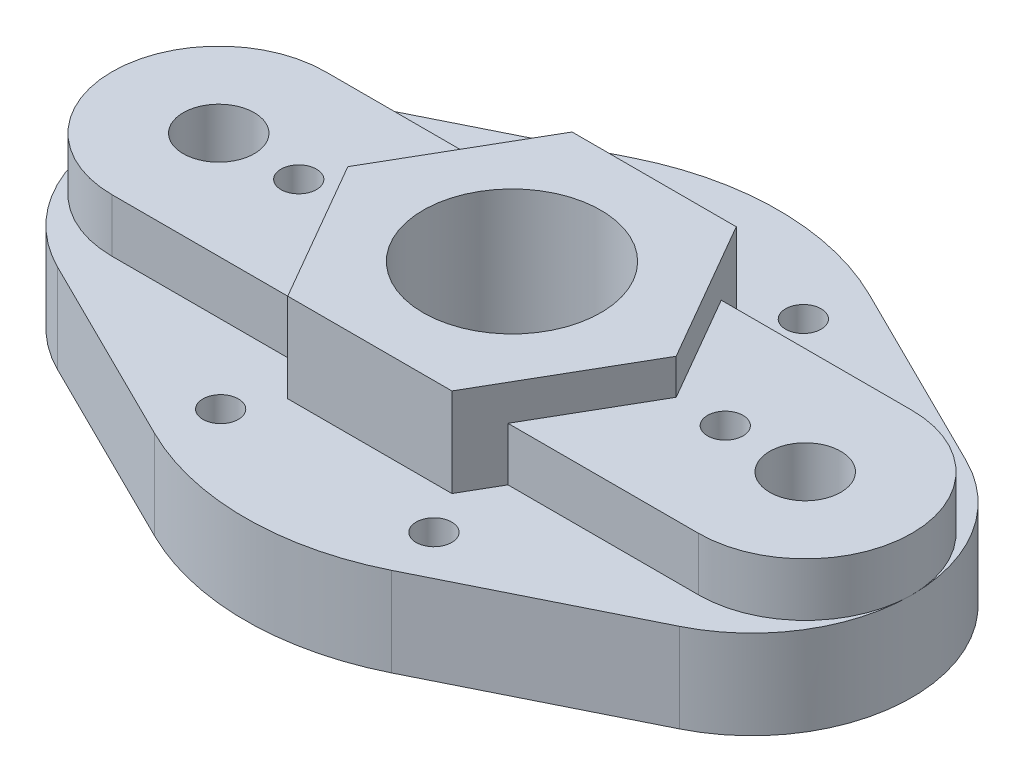
SolidWorks part; units mm, degrees
ref_plane "前视基准面" through (0, 0, 0) normal (0, 0, 1) x (1, 0, 0)
ref_plane "上视基准面" through (0, 0, 0) normal (0, 1, 0) x (1, 0, 0)
ref_plane "右视基准面" through (0, 0, 0) normal (1, 0, 0) x (0, 0, -1)
other "Configuration Table"
sketch "草图2" plane through (0, 0, 0) normal (0, 1, 0) x (1, 0, 0)
  line L0 (0, 0) -> (0, 24.5098) construction
  line L1 (0, 0) -> (45, 0) construction
  line L2 (35, 16.1245) -> (13.3333, 26.8742)
  line L3 (-35, 16.1245) -> (-13.3333, 26.8742)
  line L4 (-35, -16.1245) -> (-13.3333, -26.8742)
  line L5 (35, -16.1245) -> (13.3333, -26.8742)
  line L6 (-33, 0) -> (33, 0) construction
  line L7 (-33, 12) -> (33, 12)
  line L8 (-33, -12) -> (33, -12)
  line L10 (18.4752, 0) -> (9.2376, 16)
  line L11 (9.2376, 16) -> (-9.2376, 16)
  line L12 (-9.2376, 16) -> (-18.4752, 0)
  line L13 (-18.4752, 0) -> (-9.2376, -16)
  line L14 (-9.2376, -16) -> (9.2376, -16)
  line L15 (9.2376, -16) -> (18.4752, 0)
  arc A0 (35, -16.1245) -> (35, 16.1245) centre (27, 0) ccw
  arc A1 (13.3333, 26.8742) -> (-13.3333, 26.8742) centre (0, 0) ccw
  arc A2 (-35, -16.1245) -> (-35, 16.1245) centre (-27, 0) cw
  arc A3 (13.3333, -26.8742) -> (-13.3333, -26.8742) centre (0, 0) cw
  arc A4 (-33, 12) -> (-33, -12) centre (-33, 0) ccw
  arc A5 (33, -12) -> (33, 12) centre (33, 0) ccw
  circle A6 centre (0, 0) radius 16 construction
  point P16 (0, -30)
  point P17 (0, 30)
  point P18 (45, 0)
  point P19 (-45, 0)
  point P22 (0, 0)
  dimension "D1" = 18
  dimension "D2" = 30
  dimension "D3" = 60
  dimension "D4" = 90
  dimension "D5" = 24
  dimension "D6" = 32
extrude "凸台-拉伸1" add sketch "草图2" along normal blind 10 contours A5 L8 L15 L14 L13 A4 A2 L4 A3 L5 A0 | A5 A0 L2 A1 L3 A2 A4 L7 L12 L11 L10 region at (0, 0, -18.9941) region at (0, 0, 18.9941)
extrude "凸台-拉伸2" add sketch "草图2<3>" along normal blind 16 contours L7 A4 L8 L13 L12 | L8 A5 L7 L10 L15 region at (28.7758, 0, 0) region at (-28.7758, 0, 0)
sketch "草图2<3>" plane through (0, 0, 0) normal (0, 1, 0) x (1, 0, 0) same geometry as "草图2"
extrude "凸台-拉伸3" add sketch "草图2<4>" along normal blind 20 contours L11 L12 L7 L10 | L8 L15 L10 L7 L12 L13 | L14 L15 L8 L13 region at (0, 0, 13.9259) region at (0, 0, 0) region at (0, 0, -13.9259)
sketch "草图2<4>" plane through (0, 0, 0) normal (0, 1, 0) x (1, 0, 0) same geometry as "草图2"
sketch "草图3" plane through (0, 20, 0) normal (0, 1, 0) x (1, 0, 0)
  line L0 (0, 0) -> (0, 32.6138) construction
  circle A0 centre (0, 0) radius 10
  circle A1 centre (0, 0) radius 24 construction
  circle A2 centre (33, 0) radius 4
  circle A3 centre (-33, 0) radius 4
  circle A4 centre (24, 0) radius 2
  circle A5 centre (12, -20.7846) radius 2
  circle A6 centre (-12, -20.7846) radius 2
  circle A7 centre (-24, 0) radius 2
  circle A8 centre (-12, 20.7846) radius 2
  circle A9 centre (12, 20.7846) radius 2
  dimension "D1" = 20
  dimension "D2" = 48
  dimension "D3" = 8
  dimension "D5" = 4
  dimension "D4" = 66
  dimension "D6" = 6
extrude "切除-拉伸1" cut sketch "草图3" against normal through all
